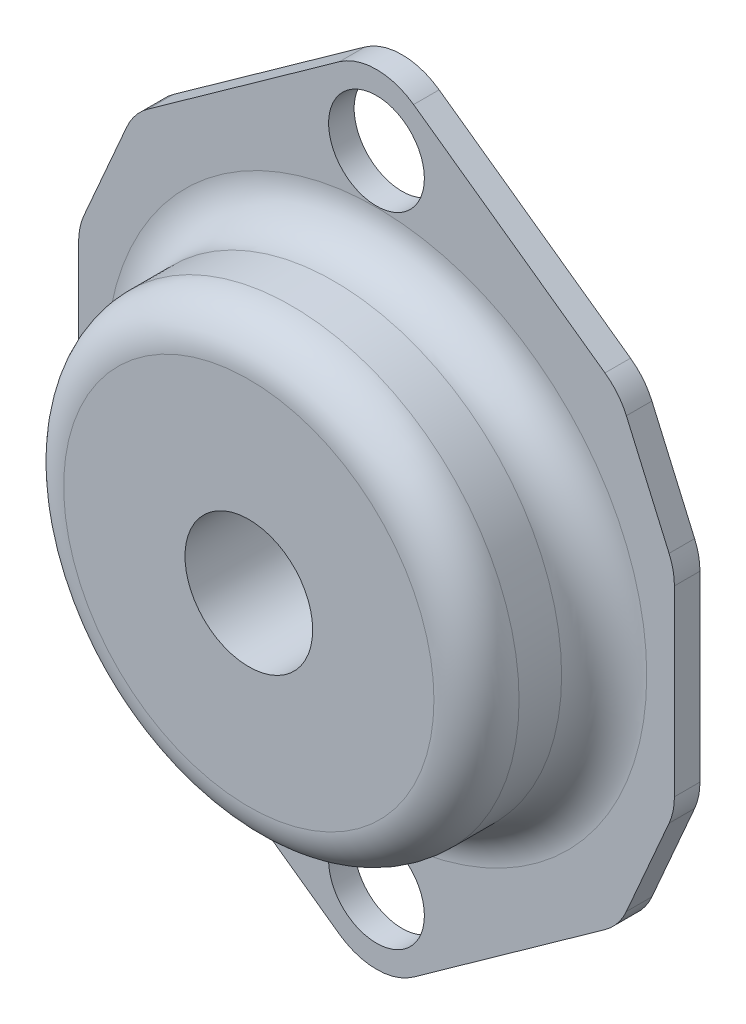
SolidWorks part; units mm, degrees
ref_plane "正面" through (0, 0, 0) normal (0, 0, 1) x (1, 0, 0)
ref_plane "平面" through (0, 0, 0) normal (0, 1, 0) x (1, 0, 0)
ref_plane "右側面" through (0, 0, 0) normal (1, 0, 0) x (0, 0, -1)
sketch "ｽｹｯﾁ1" plane through (0, 0, 0) normal (0, 0, 1) x (1, 0, 0)
  line L0 (0, -19) -> (0, 19)
  line L1 (-3, 0) -> (3, 0)
  line L2 (0, -15) -> (0, 15)
  line L3 (-14, -4.9172) -> (-14, 4.9172)
  line L4 (-14, 4.9172) -> (-11.4113, 10.8478)
  line L5 (-11.4113, 10.8478) -> (0, 19)
  line L6 (14, -4.9172) -> (14, 4.9172)
  line L7 (14, 4.9172) -> (11.4113, 10.8478)
  line L8 (11.4113, 10.8478) -> (0, 19)
  line L9 (14, -4.9172) -> (11.4113, -10.8478)
  line L10 (11.4113, -10.8478) -> (0, -19)
  line L11 (-11.4113, -10.8478) -> (0, -19)
  line L12 (-14, -4.9172) -> (-11.4113, -10.8478)
  circle A0 centre (0, 0) radius 3
  circle A1 centre (0, 15) radius 2.25
  circle A2 centre (0, -15) radius 2.25
  point P4 (0, 0)
  point P8 (0, 0)
  point P13 (0, 0)
  dimension "D1" = 6
  dimension "D3" = 4.5
  dimension "D4" = 4.5
  dimension "D2" = 15
extrude "ﾎﾞｽ - 押し出し1" add sketch "ｽｹｯﾁ1" along normal blind 1.2 contours A2 L2 A0 A1 L0 L5 L4 L3 L12 L11 | A2 L0 L10 L9 L6 L7 L8 A1 L2 A0 region at (-6.3897, 0, 0) region at (6.3897, 0, 0)
fillet "ﾌｨﾚｯﾄ1" radius 3 10 edges at (-14, -4.9172, 0.6) (-11.4113, -10.8478, 0.6) (0, -19, 0.6) (11.4113, -10.8478, 0.6) (14, -4.9172, 0.6) (14, 4.9172, 0.6) (11.4113, 10.8478, 0.6) (-14, 4.9172, 0.6) (-11.4113, 10.8478, 0.6) (0, 19, 0.6)
sketch "ｽｹｯﾁ2" plane through (0, 0, 1.2) normal (0, 0, 1) x (1, 0, 0)
  circle A0 centre (0, 0) radius 10.7
  dimension "D1" = 21.4
extrude "ﾎﾞｽ - 押し出し2" add sketch "ｽｹｯﾁ2" along normal blind 6
extrude "ｶｯﾄ - 押し出し1" cut sketch "ｽｹｯﾁ1<3>" along normal blind 20 contours A0
sketch "ｽｹｯﾁ1<3>" plane through (0, 0, 0) normal (0, 0, 1) x (1, 0, 0) same geometry as "ｽｹｯﾁ1"
fillet "ﾌｨﾚｯﾄ2" radius 2 2 edges at (10.7, 0, 7.2) (10.7, 0, 1.2)
